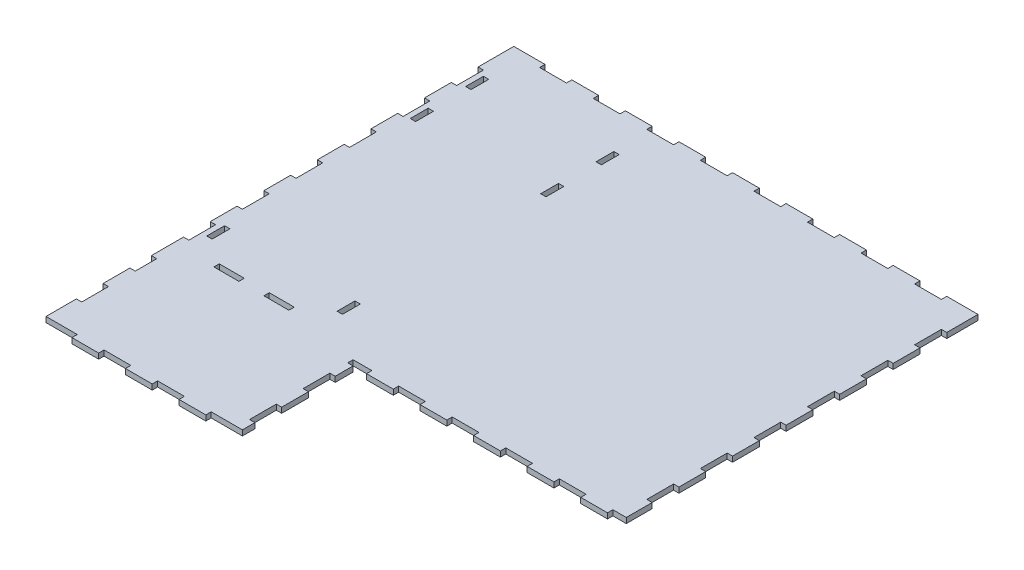
SolidWorks part; units mm, degrees
ref_plane "Alzado" through (0, 0, 0) normal (0, 0, 1) x (1, 0, 0)
ref_plane "Planta" through (0, 0, 0) normal (0, 1, 0) x (1, 0, 0)
ref_plane "Vista lateral" through (0, 0, 0) normal (1, 0, 0) x (0, 0, -1)
sketch "Croquis1" plane through (0, 0, 0) normal (0, 1, 0) x (1, 0, 0)
  line L0 (17.5, 0) -> (32.5, 0)
  line L1 (0, 3) -> (0, 20)
  line L2 (0, 265) -> (17.5, 265)
  line L3 (260, 265) -> (260, 247.5)
  line L4 (252.5, 65) -> (237.5, 65)
  line L5 (110, 65) -> (110, 55)
  line L6 (110, 3) -> (110, 10)
  line L7 (9, 87.0377) -> (9, 74.0377) construction
  line L8 (47.5, 0) -> (47.5, 3)
  line L9 (47.5, 3) -> (32.5, 3)
  line L10 (32.5, 3) -> (32.5, 0)
  line L11 (6, 232.0377) -> (9, 232.0377)
  line L12 (17.5, 0) -> (17.5, 3)
  line L13 (17.5, 3) -> (0, 3)
  line L14 (9, 74.0377) -> (23, 74.0377) construction
  line L15 (92.5, 3) -> (110, 3)
  line L16 (92.5, 0) -> (92.5, 3)
  line L17 (77.5, 3) -> (77.5, 0)
  line L18 (62.5, 3) -> (77.5, 3)
  line L19 (62.5, 0) -> (62.5, 3)
  line L20 (110, 25) -> (107, 25)
  line L21 (107, 25) -> (107, 10)
  line L22 (107, 10) -> (110, 10)
  line L23 (9, 232.0377) -> (9, 242)
  line L24 (107, 55) -> (110, 55)
  line L25 (107, 40) -> (107, 55)
  line L26 (110, 40) -> (107, 40)
  line L27 (9, 242) -> (6, 242)
  line L28 (177.5, 65) -> (177.5, 68)
  line L29 (177.5, 68) -> (162.5, 68)
  line L30 (162.5, 68) -> (162.5, 65)
  line L31 (162.5, 65) -> (147.5, 65)
  line L32 (147.5, 65) -> (147.5, 68)
  line L33 (147.5, 68) -> (132.5, 68)
  line L34 (132.5, 68) -> (132.5, 65)
  line L35 (132.5, 65) -> (117.5, 65)
  line L36 (117.5, 65) -> (117.5, 68)
  line L37 (117.5, 68) -> (107, 68)
  line L38 (107, 68) -> (107, 65)
  line L39 (107, 65) -> (110, 65)
  line L40 (6, 242) -> (6, 232.0377)
  line L41 (260, 157.5) -> (257, 157.5)
  line L42 (252.5, 68) -> (260, 68)
  line L43 (252.5, 65) -> (252.5, 68)
  line L44 (237.5, 68) -> (237.5, 65)
  line L45 (222.5, 68) -> (237.5, 68)
  line L46 (222.5, 65) -> (222.5, 68)
  line L47 (207.5, 68) -> (207.5, 65)
  line L48 (192.5, 68) -> (207.5, 68)
  line L49 (192.5, 65) -> (192.5, 68)
  line L50 (257, 157.5) -> (257, 142.5)
  line L51 (257, 142.5) -> (260, 142.5)
  line L52 (260, 142.5) -> (260, 127.5)
  line L53 (260, 127.5) -> (257, 127.5)
  line L54 (257, 127.5) -> (257, 112.5)
  line L55 (257, 112.5) -> (260, 112.5)
  line L56 (260, 112.5) -> (260, 97.5)
  line L57 (260, 97.5) -> (257, 97.5)
  line L58 (257, 97.5) -> (257, 82.5)
  line L59 (257, 82.5) -> (260, 82.5)
  line L60 (6, 232.0377) -> (6, 211.0377) construction
  line L61 (257, 247.5) -> (260, 247.5)
  line L62 (257, 232.5) -> (257, 247.5)
  line L63 (260, 232.5) -> (257, 232.5)
  line L64 (257, 217.5) -> (260, 217.5)
  line L65 (257, 202.5) -> (257, 217.5)
  line L66 (260, 202.5) -> (257, 202.5)
  line L67 (257, 187.5) -> (260, 187.5)
  line L68 (257, 172.5) -> (257, 187.5)
  line L69 (260, 172.5) -> (257, 172.5)
  line L70 (137.5, 265) -> (137.5, 262)
  line L71 (137.5, 262) -> (152.5, 262)
  line L72 (152.5, 262) -> (152.5, 265)
  line L73 (152.5, 265) -> (167.5, 265)
  line L74 (167.5, 265) -> (167.5, 262)
  line L75 (167.5, 262) -> (182.5, 262)
  line L76 (182.5, 262) -> (182.5, 265)
  line L77 (182.5, 265) -> (197.5, 265)
  line L78 (197.5, 265) -> (197.5, 262)
  line L79 (197.5, 262) -> (212.5, 262)
  line L80 (212.5, 262) -> (212.5, 265)
  line L81 (212.5, 265) -> (227.5, 265)
  line L82 (227.5, 265) -> (227.5, 262)
  line L83 (227.5, 262) -> (242.5, 262)
  line L84 (242.5, 262) -> (242.5, 265)
  line L86 (17.5, 262) -> (17.5, 265)
  line L87 (32.5, 262) -> (17.5, 262)
  line L88 (32.5, 265) -> (32.5, 262)
  line L89 (47.5, 262) -> (47.5, 265)
  line L90 (62.5, 262) -> (47.5, 262)
  line L91 (62.5, 265) -> (62.5, 262)
  line L92 (77.5, 262) -> (77.5, 265)
  line L93 (92.5, 262) -> (77.5, 262)
  line L94 (92.5, 265) -> (92.5, 262)
  line L95 (107.5, 262) -> (107.5, 265)
  line L96 (122.5, 262) -> (107.5, 262)
  line L97 (122.5, 265) -> (122.5, 262)
  line L98 (0, 140) -> (3, 140)
  line L99 (3, 140) -> (3, 155)
  line L100 (3, 155) -> (0, 155)
  line L101 (0, 155) -> (0, 170)
  line L102 (0, 170) -> (3, 170)
  line L103 (3, 170) -> (3, 185)
  line L104 (3, 185) -> (0, 185)
  line L105 (0, 185) -> (0, 200)
  line L106 (0, 200) -> (3, 200)
  line L107 (3, 200) -> (3, 215)
  line L108 (3, 215) -> (0, 215)
  line L109 (0, 215) -> (0, 230)
  line L110 (0, 230) -> (3, 230)
  line L111 (3, 230) -> (3, 245)
  line L112 (3, 245) -> (0, 245)
  line L113 (6, 211.0377) -> (6, 201.0377)
  line L114 (3, 20) -> (0, 20)
  line L115 (3, 35) -> (3, 20)
  line L116 (0, 35) -> (3, 35)
  line L117 (3, 50) -> (0, 50)
  line L118 (3, 62) -> (3, 50)
  line L119 (32.5, 265) -> (47.5, 265)
  line L120 (3, 80) -> (0, 80)
  line L121 (3, 95) -> (3, 80)
  line L122 (0, 95) -> (3, 95)
  line L123 (3, 110) -> (0, 110)
  line L124 (3, 125) -> (3, 110)
  line L125 (0, 125) -> (3, 125)
  line L127 (0, 62) -> (3, 62)
  line L128 (62.5, 265) -> (77.5, 265)
  line L129 (92.5, 265) -> (107.5, 265)
  line L130 (122.5, 265) -> (137.5, 265)
  line L131 (6, 97.0377) -> (6, 87.0377)
  line L132 (6, 97.0377) -> (9, 97.0377)
  line L133 (9, 97.0377) -> (9, 87.0377)
  line L134 (242.5, 265) -> (260, 265)
  line L135 (0, 245) -> (0, 265)
  line L136 (9, 87.0377) -> (6, 87.0377)
  line L139 (0, 125) -> (0, 140)
  line L140 (0, 95) -> (0, 110)
  line L141 (0, 62) -> (0, 80)
  line L142 (0, 35) -> (0, 50)
  line L143 (47.5, 0) -> (62.5, 0)
  line L144 (77.5, 0) -> (92.5, 0)
  line L145 (23, 74.0377) -> (23, 77.0377)
  line L146 (23, 77.0377) -> (37, 77.0377)
  line L147 (110, 40) -> (110, 25)
  line L148 (37, 77.0377) -> (37, 74.0377)
  line L149 (37, 74.0377) -> (23, 74.0377)
  line L150 (192.5, 65) -> (177.5, 65)
  line L151 (222.5, 65) -> (207.5, 65)
  line L152 (260, 82.5) -> (260, 68)
  line L154 (6, 211.0377) -> (9, 211.0377)
  line L155 (260, 172.5) -> (260, 157.5)
  line L156 (260, 202.5) -> (260, 187.5)
  line L157 (260, 232.5) -> (260, 217.5)
  line L158 (9, 211.0377) -> (9, 201.0377)
  line L159 (9, 201.0377) -> (6, 201.0377)
  line L161 (79, 201.0377) -> (82, 201.0377)
  line L162 (79, 211.0377) -> (79, 201.0377)
  line L163 (82, 211.0377) -> (79, 211.0377)
  line L164 (51, 74.0377) -> (65, 74.0377)
  line L165 (51, 77.0377) -> (51, 74.0377)
  line L166 (65, 77.0377) -> (51, 77.0377)
  line L167 (65, 74.0377) -> (65, 77.0377)
  line L170 (79, 87.0377) -> (82, 87.0377)
  line L171 (79, 97.0377) -> (79, 87.0377)
  line L172 (82, 97.0377) -> (79, 97.0377)
  line L173 (82, 97.0377) -> (82, 87.0377)
  line L175 (82, 211.0377) -> (82, 201.0377)
  line L177 (79, 232.0377) -> (82, 232.0377)
  line L178 (79, 242.0377) -> (79, 232.0377)
  line L179 (82, 242.0377) -> (79, 242.0377)
  line L182 (82, 242.0377) -> (82, 232.0377)
  dimension "D5" = 3
  dimension "D6" = 15
  dimension "D7" = 15
  dimension "D8" = 13
  dimension "D9" = 3
  dimension "D10" = 15
  dimension "D11" = 21
  dimension "D12" = 3
  dimension "D13" = 15
  dimension "D14" = 15
  dimension "D15" = 15
  dimension "D16" = 15
  dimension "D18" = 3
  dimension "D19" = 15
  dimension "D20" = 15
  dimension "D21" = 15
  dimension "D22" = 15
  dimension "D23" = 15
  dimension "D25" = 3
  dimension "D26" = 15
  dimension "D27" = 15
  dimension "D28" = 15
  dimension "D29" = 15
  dimension "D30" = 15
  dimension "D31" = 15
  dimension "D32" = 15
  dimension "D34" = 3
  dimension "D35" = 15
  dimension "D36" = 15
  dimension "D37" = 15
  dimension "D38" = 15
  dimension "D39" = 15
  dimension "D40" = 15
  dimension "D43" = 10
  dimension "D44" = 104
  dimension "D45" = 10
  dimension "D48" = 14
extrude "Saliente-Extruir1" add sketch "Croquis1" along normal blind 3
